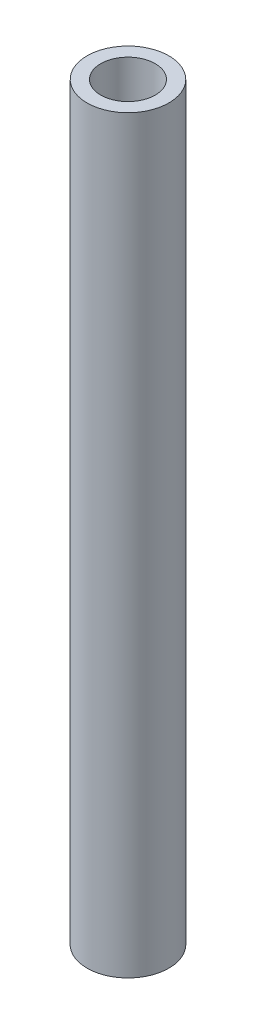
SolidWorks part; units mm, degrees
material "1023 Arkusz stali węglowej (SS)"
ref_plane "Płaszczyzna przednia" through (0, 0, 0) normal (0, 0, 1) x (1, 0, 0)
ref_plane "Płaszczyzna górna" through (0, 0, 0) normal (0, 1, 0) x (1, 0, 0)
ref_plane "Płaszczyzna prawa" through (0, 0, 0) normal (1, 0, 0) x (0, 0, -1)
sketch "Szkic1" plane through (0, 0, 0) normal (0, 1, 0) x (1, 0, 0)
  circle A0 centre (0, 0) radius 6
extrude "Dodanie-wyciągnięcie1" add sketch "Szkic1" along normal blind 110
sketch "Szkic2" plane through (0, 110, 0) normal (0, 1, 0) x (1, 0, 0)
  circle A0 centre (0, 0) radius 4
  dimension "D1" = 8
extrude "Wytnij-wyciągnięcie1" cut sketch "Szkic2" against normal blind 30 contours A0
sketch "Szkic5" plane through (0, 0, 0) normal (0, -1, 0) x (1, 0, 0)
  circle A0 centre (0, 0) radius 4
  dimension "D1" = 8
extrude "Wytnij-wyciągnięcie2" cut sketch "Szkic5" against normal blind 30
